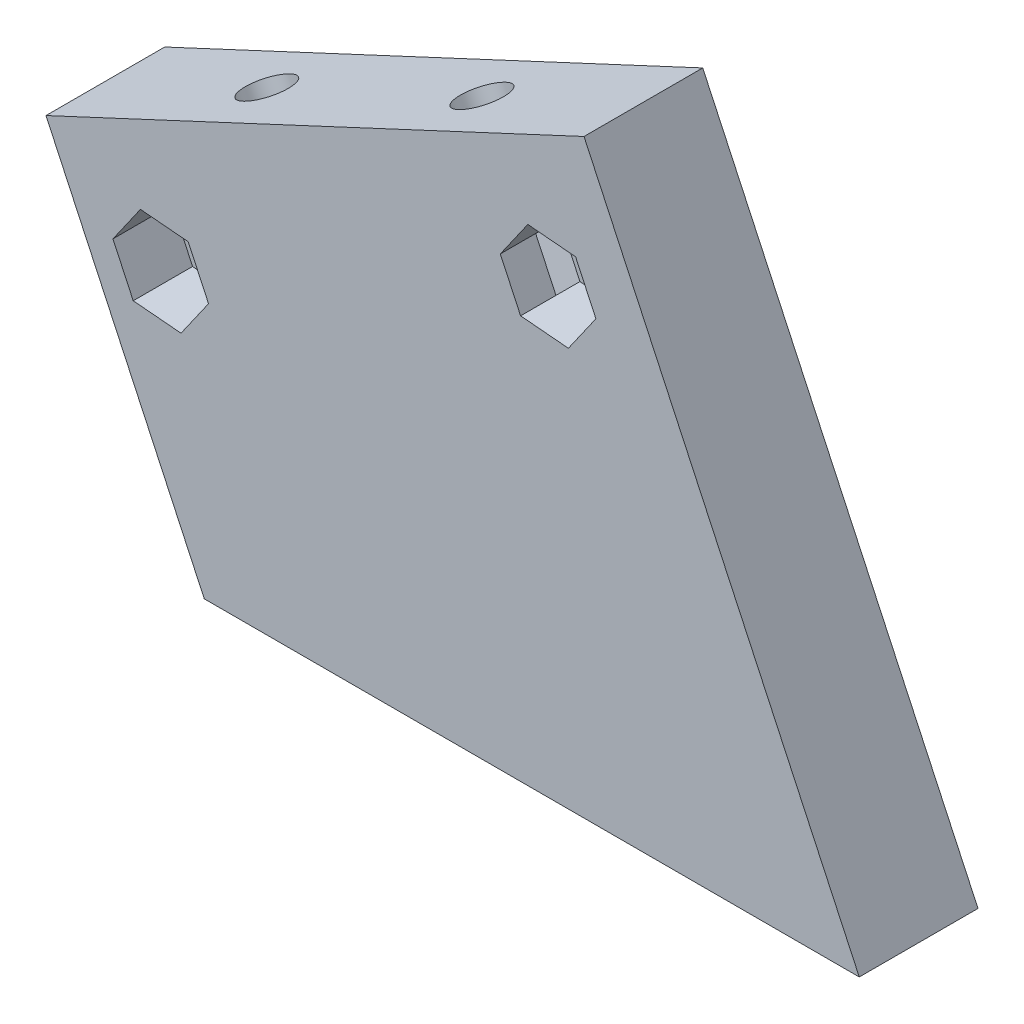
SolidWorks part; units mm, degrees
ref_plane "Front Plane" through (0, 0, 0) normal (0, 0, 1) x (1, 0, 0)
ref_plane "Top Plane" through (0, 0, 0) normal (0, 1, 0) x (1, 0, 0)
ref_plane "Right Plane" through (0, 0, 0) normal (1, 0, 0) x (0, 0, -1)
sketch "Sketch1" plane through (0, 0, 0) normal (0, 0, 1) x (1, 0, 0)
  line L0 (110.3324, 0.0035) -> (87.1479, 49.7228)
  line L2 (87.1479, 49.7228) -> (41.8325, 28.5919)
  line L3 (41.8325, 28.5919) -> (55.1635, 0.0035)
  line L4 (55.1635, 0.0035) -> (110.3324, 0.0035)
  line L6 (210.9886, 107.4706) -> (-151.5345, -61.5767) construction
  point P2 (0, 0)
  point P6 (101.7306, 25.5862)
  point P8 (0, 0)
  dimension "D1" = 50
extrude "Boss-Extrude1" add sketch "Sketch1" against normal blind 10
sketch "Sketch2" plane through (-3.4798, 7.4624, 0) normal (-0.4226, 0.9063, 0) x (0.9063, 0.4226, 0)
  line L0 (49.9966, 5) -> (99.9966, 5) construction
  line L1 (49.9966, 10) -> (49.9966, 0) construction
  line L2 (99.9966, 10) -> (99.9966, 0) construction
  line L3 (74.9966, 10) -> (74.9966, 0) construction
  line L4 (84.9966, 0.9585) -> (88.4966, 2.9793)
  line L5 (88.4966, 2.9793) -> (88.4966, 7.0207)
  line L6 (88.4966, 7.0207) -> (84.9966, 9.0415)
  line L7 (84.9966, 9.0415) -> (81.4966, 7.0207)
  line L8 (81.4966, 7.0207) -> (81.4966, 2.9793)
  line L9 (81.4966, 2.9793) -> (84.9966, 0.9585)
  line L10 (99.9966, 10) -> (49.9966, 10) construction
  line L11 (99.9966, 0) -> (49.9966, 0) construction
  line L12 (68.4966, 2.9793) -> (64.9966, 0.9585)
  line L13 (64.9966, 0.9585) -> (61.4966, 2.9793)
  line L14 (68.4966, 7.0207) -> (68.4966, 2.9793)
  line L15 (64.9966, 9.0415) -> (68.4966, 7.0207)
  line L16 (61.4966, 7.0207) -> (64.9966, 9.0415)
  line L17 (61.4966, 2.9793) -> (61.4966, 7.0207)
  circle A0 centre (84.9966, 5) radius 3.5 construction
  circle A1 centre (84.9966, 5) radius 2
  circle A2 centre (64.9966, 5) radius 3.5 construction
  circle A3 centre (64.9966, 5) radius 2
  dimension "D3" = 4
  dimension "D1" = 15
  dimension "D2" = 7
extrude "Cut-Extrude1" cut sketch "Sketch2" against normal through all contours A3 | A1 region at (73.5533, 43.3835, -5) region at (55.4272, 34.9312, -5)
extrude "Cut-Extrude2" cut sketch "Sketch2<3>" against normal through all from offset 4 offset against normal yes
sketch "Sketch2<3>" plane through (-3.4798, 7.4624, 0) normal (-0.4226, 0.9063, 0) x (0.9063, 0.4226, 0) same geometry as "Sketch2"
sketch "Sketch3" plane through (0, 0.0035, 0) normal (0, -1, 0) x (1, 0, 0)
  line L0 (110.3324, -5) -> (55.1635, -5) construction
  line L1 (110.3324, -10) -> (110.3324, 0) construction
  line L2 (55.1635, -10) -> (55.1635, 0) construction
  circle A0 centre (82.748, -5) radius 2
  circle A1 centre (102.8324, -5) radius 2
  dimension "D1" = 4
  dimension "D2" = 4
  dimension "D3" = 7.5
extrude "Cut-Extrude3" cut sketch "Sketch3" against normal blind 10
sketch "Sketch4" plane through (0, 0, 0) normal (0, 0, 1) x (1, 0, 0)
  line L0 (110.3324, 0.0035) -> (87.1479, 49.7228) construction
  line L1 (88.1497, 36.9265) -> (86.4417, 40.5893)
  line L2 (86.4417, 40.5893) -> (82.4157, 40.9416)
  line L3 (82.4157, 40.9416) -> (80.0976, 37.631)
  line L4 (80.0976, 37.631) -> (81.8056, 33.9682)
  line L5 (81.8056, 33.9682) -> (85.8317, 33.616)
  line L6 (85.8317, 33.616) -> (88.1497, 36.9265)
  line L7 (87.1479, 49.7228) -> (41.8325, 28.5919) construction
  line L8 (55.5227, 21.7123) -> (53.8147, 25.3751)
  line L9 (53.8147, 25.3751) -> (49.7886, 25.7273)
  line L10 (49.7886, 25.7273) -> (47.4705, 22.4167)
  line L11 (47.4705, 22.4167) -> (49.1785, 18.7539)
  line L12 (49.1785, 18.7539) -> (53.2046, 18.4017)
  line L13 (53.2046, 18.4017) -> (55.5227, 21.7123)
  line L14 (87.1479, 49.7228) -> (41.8325, 28.5919) construction
  line L15 (41.8325, 28.5919) -> (55.1635, 0.0035) construction
  circle A0 centre (84.1237, 37.2788) radius 2
  circle A1 centre (84.1237, 37.2788) radius 3.5 construction
  circle A2 centre (51.4966, 22.0645) radius 2
  circle A3 centre (51.4966, 22.0645) radius 3.5 construction
  dimension "D4" = 4
  dimension "D7" = 4
  dimension "D1" = 8
  dimension "D2" = 10
  dimension "D3" = 7
  dimension "D5" = 0
  dimension "D6" = 7
  dimension "D8" = 10
  dimension "D9" = 6
extrude "Cut-Extrude4" cut sketch "Sketch4" against normal blind 10 contours A0 | A2 region at (84.1237, 37.2788, 0) region at (51.4966, 22.0645, 0)
extrude "Cut-Extrude5" cut sketch "Sketch4<3>" against normal blind 5 from surface starting at face at (86.1237, 37.2788, 0)
sketch "Sketch4<3>" plane through (0, 0, 0) normal (0, 0, 1) x (1, 0, 0) same geometry as "Sketch4"
